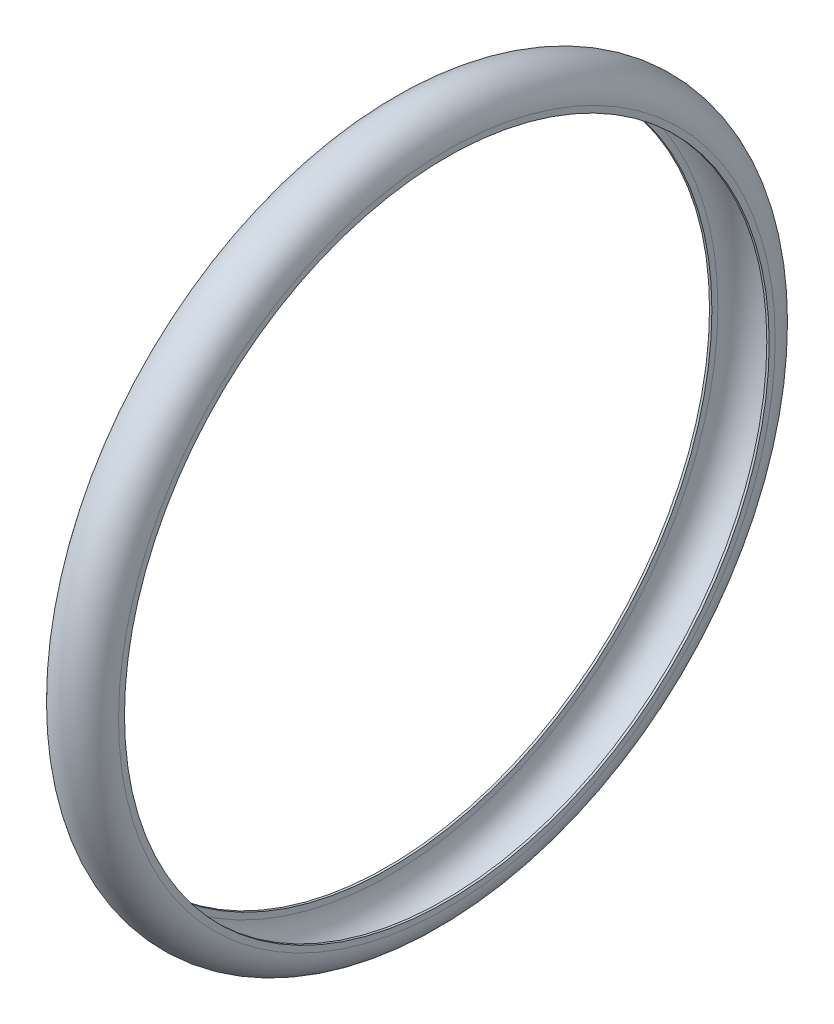
SolidWorks part; units mm, degrees
ref_plane "Front Plane" through (0, 0, 0) normal (0, 0, 1) x (1, 0, 0)
ref_plane "Top Plane" through (0, 0, 0) normal (0, 1, 0) x (1, 0, 0)
ref_plane "Right Plane" through (0, 0, 0) normal (1, 0, 0) x (0, 0, -1)
sketch "Sketch1" plane through (0, 0, 0) normal (1, 0, 0) x (0, 0, -1)
  circle A0 centre (0, 0) radius 270
  circle A1 centre (0, 0) radius 300
extrude "Boss-Extrude1" add sketch "Sketch1" along normal blind 50
fillet "Fillet1" 2 edges at (50, 0, -300) (0, 0, -300) type full round first side face at (50, 0, -300) second side face at (0, 0, -300) middle face at (50, 0, -300)
shell "Shell1" thickness 2 removed face at (50, 0, -270)
